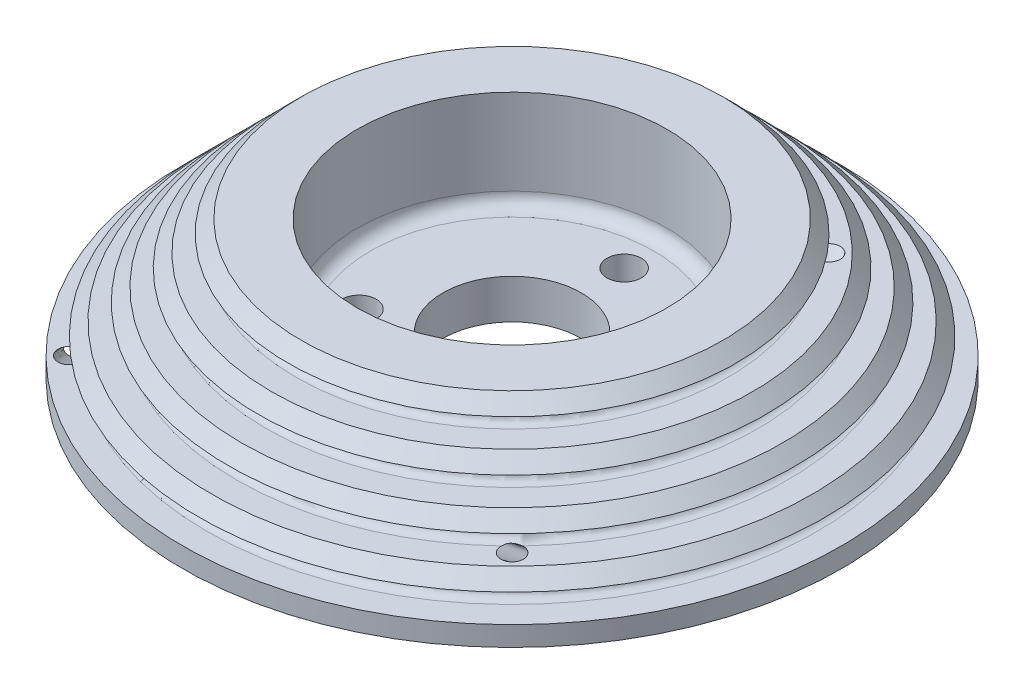
SolidWorks part; units mm, degrees
ref_plane "Front Plane" through (0, 0, 0) normal (0, 0, 1) x (1, 0, 0)
ref_plane "Top Plane" through (0, 0, 0) normal (0, 1, 0) x (1, 0, 0)
ref_plane "Right Plane" through (0, 0, 0) normal (1, 0, 0) x (0, 0, -1)
sketch "Sketch1" plane through (0, 0, 0) normal (0, 0, 1) x (1, 0, 0)
  line L0 (0, 0) -> (0, 21)
  line L1 (0, 21) -> (-32, 21)
  line L2 (-32, 21) -> (-50, 3)
  line L3 (-50, 3) -> (-50, 0)
  line L4 (-50, 0) -> (0, 0)
  dimension "D1" = 50
  dimension "D2" = 21
  dimension "D3" = 45
  dimension "D4" = 3
revolve "Revolve1" add sketch "Sketch1" angle 360 about L0
sketch "Sketch2" plane through (0, 0, 0) normal (0, 0, 1) x (1, 0, 0)
  line L0 (0, 0) -> (0, 23.1188)
  line L1 (-32, 21) -> (-50, 3) construction
  line L2 (-36.5, 19) -> (-31.5, 19)
  line L3 (-36.5, 19) -> (-36.5, 16.5)
  line L4 (-36.5, 16.5) -> (-31.5, 16.5)
  line L5 (-31.5, 19) -> (-31.5, 16.5)
  line L6 (-50, 5.5) -> (-45, 5.5)
  line L7 (-50, 5.5) -> (-50, 3)
  line L8 (-50, 3) -> (-45, 3)
  line L9 (-45, 5.5) -> (-45, 3)
  line L10 (-32, 21) -> (-50, 3)
  line L12 (32, 21) -> (-32, 21) construction
  line L13 (50, 3) -> (-50, 3) construction
  line L15 (-41, 14.5) -> (-36, 14.5)
  line L16 (-41, 14.5) -> (-41, 12)
  line L17 (-41, 12) -> (-36, 12)
  line L18 (-36, 14.5) -> (-36, 12)
  line L19 (-45.5, 10) -> (-40.5, 10)
  line L20 (-45.5, 10) -> (-45.5, 7.5)
  line L21 (-45.5, 7.5) -> (-40.5, 7.5)
  line L22 (-40.5, 10) -> (-40.5, 7.5)
  point P19 (-38.5, 14.5)
  point P26 (-43, 10)
  point P27 (-47.5, 5.5)
  point P28 (-34, 19)
  dimension "D1" = 2.5
  dimension "D2" = 2.5
  dimension "D3" = 5
  dimension "D4" = 5
  dimension "D5" = 5
  dimension "D6" = 2
  dimension "D7" = 2.5
  dimension "D8" = 2
  dimension "D9" = 5
  dimension "D10" = 2.5
  dimension "D11" = 2
revolve "Cut-Revolve1" cut sketch "Sketch2" angle 360 about L0 region at (-46.9444, 4.1111, 0) region at (-42.4444, 8.6111, 0) region at (-37.9444, 13.1111, 0) region at (-33.4444, 17.6111, 0)
fillet "Fillet1" radius 1.25 8 edges at (0, 3, -45) (0, 5.5, -45) (0, 7.5, -40.5) (0, 10, -40.5) (0, 12, -36) (0, 14.5, -36) (0, 16.5, -31.5) (0, 19, -31.5)
sketch "Sketch3" plane through (0, 21, 0) normal (0, 1, 0) x (1, 0, 0)
  line L0 (0, 0) -> (44.738, 0) construction
  line L1 (0, 0) -> (32.1015, 32.1015)
  line L2 (0, 0) -> (32.1015, -32.1015)
  dimension "D1" = 45
ref_plane "top inner hole" through (0, 0, 0) normal (0.7071, 0, 0.7071) x (0.7071, 0, -0.7071)
ref_plane "bottom outer hole" through (0, 0, 0) normal (-0.7071, 0, 0.7071) x (0.7071, 0, 0.7071)
sketch "Sketch4" plane through (0, 0, 0) normal (0.7071, 0, 0.7071) x (0.7071, 0, -0.7071)
  line L0 (34, 16.5) -> (31.0906, 0)
  line L1 (36.5, 16.5) -> (-36.5, 16.5) construction
  line L2 (-50, 0) -> (50, 0) construction
  line L3 (34, 16.5) -> (33.8108, 15.4272)
  line L4 (34, 16.5) -> (34.2703, 18.0328)
  dimension "D1" = 2.5
  dimension "D2" = 80
sketch "Sketch5" plane through (0, 0, 0) normal (-0.7071, 0, 0.7071) x (0.7071, 0, 0.7071)
  line L0 (43, 7.5) -> (40.2702, 0)
  line L1 (45.5, 7.5) -> (-45.5, 7.5) construction
  line L2 (-50, 0) -> (50, 0) construction
  line L3 (43, 7.5) -> (41.2173, 2.6022)
  line L4 (43, 7.5) -> (43.3748, 8.5297)
  dimension "D1" = 2.5
  dimension "D2" = 70
sketch "Sketch6" plane through (0, 0, 0) normal (-0.7071, 0, 0.7071) x (0.7071, 0, 0.7071)
  line L0 (-38.5, 12) -> (-34.1324, 0)
  line L1 (41, 12) -> (-41, 12) construction
  line L2 (-50, 0) -> (50, 0) construction
  line L3 (-38.5, 12) -> (-37.0691, 8.0687)
  line L4 (-38.5, 12) -> (-38.9783, 13.3142)
  dimension "D1" = 70
  dimension "D2" = 2.5
sketch "Sketch7" plane through (0, 0, 0) normal (0.7071, 0, 0.7071) x (0.7071, 0, -0.7071)
  line L0 (-47.5008, 3) -> (-46.4089, 0)
  line L1 (50, 3) -> (-50, 3) construction
  line L2 (-50, 0) -> (50, 0) construction
  line L3 (-47.5008, 3) -> (-45.6338, -2.1294)
  line L4 (-47.5008, 3) -> (-47.9973, 4.3643)
  dimension "D1" = 2.4992
  dimension "D2" = 70
sketch "Sketch8" plane through (0, 16.5, 0) normal (0, 1, 0) x (1, 0, 0)
  circle A0 centre (24.0416, 24.0416) radius 1.7
  dimension "D1" = 3.4
sketch "Sketch9" plane through (0, 7.5, 0) normal (0, 1, 0) x (1, 0, 0)
  circle A0 centre (30.4056, -30.4056) radius 1.7
  dimension "D1" = 3.4
sketch "Sketch10" plane through (0, 3, 0) normal (0, 1, 0) x (1, 0, 0)
  circle A0 centre (-33.5881, -33.5881) radius 1.7
  dimension "D1" = 3.4
sketch "Sketch11" plane through (0, 12, 0) normal (0, 1, 0) x (1, 0, 0)
  circle A0 centre (-27.2236, 27.2236) radius 1.7
  point P3 (0, 0)
  dimension "D1" = 3.4
sketch "Sketch13" plane through (0, 21, 0) normal (0, 1, 0) x (1, 0, 0)
  circle A0 centre (0, 0) radius 23.5
  dimension "D1" = 47
extrude "Cut-Extrude2" cut sketch "Sketch13" against normal blind 15
sketch "Sketch14" plane through (0, 6, 0) normal (0, 1, 0) x (1, 0, 0)
  line L0 (0, 0) -> (0, 23.5) construction
  line L1 (0, 0) -> (20.3516, -11.75) construction
  line L2 (0, 0) -> (-20.3516, -11.75) construction
  circle A0 centre (0, 17) radius 2.6
  circle A1 centre (0, 0) radius 23.5 construction
  circle A2 centre (14.7224, -8.5) radius 2.6
  circle A3 centre (-14.7224, -8.5) radius 2.6
  circle A4 centre (0, 0) radius 10.5
  circle A5 centre (0, 0) radius 19.6
  point P6 (0, 19.6)
  point P16 (0, 0)
  dimension "D1" = 5.2
  dimension "D3" = 21
  dimension "D4" = 17
  dimension "D5" = 19.6
  dimension "D2" = 3
extrude "Cut-Extrude3" cut sketch "Sketch14" against normal through all contours A0 | A3 | A4 | A2 region at (0, 6, -17) region at (-14.7224, 6, 8.5) region at (14.7224, 6, 8.5) region at (0, 6, 0)
fillet "Fillet2" radius 2 1 edges at (0, 6, 23.5)
sketch "Sketch12" plane through (0, 21, 0) normal (0, 1, 0) x (1, 0, 0)
  line L0 (0, 0) -> (0, 13.8549) construction
  line L1 (6.188, 5.3047) -> (9.2093, 7.049)
  line L2 (-1.5, 8.0113) -> (1.5, 8.0113)
  line L3 (-1.5, 8.0113) -> (-1.5, 11.5)
  line L4 (-1.5, 11.5) -> (1.5, 11.5)
  line L5 (1.5, 8.0113) -> (1.5, 11.5)
  line L6 (6.188, 5.3047) -> (7.688, 2.7066)
  line L7 (7.688, 2.7066) -> (10.7093, 4.451)
  line L8 (9.2093, 7.049) -> (10.7093, 4.451)
  line L9 (0, 0) -> (11.9987, 6.9274) construction
  line L10 (7.688, -2.7066) -> (10.7093, -4.451)
  line L11 (7.688, -2.7066) -> (6.188, -5.3047)
  line L12 (6.188, -5.3047) -> (9.2093, -7.049)
  line L13 (10.7093, -4.451) -> (9.2093, -7.049)
  line L14 (0, 0) -> (11.9987, -6.9274) construction
  line L15 (1.5, -8.0113) -> (1.5, -11.5)
  line L16 (1.5, -8.0113) -> (-1.5, -8.0113)
  line L17 (-1.5, -8.0113) -> (-1.5, -11.5)
  line L18 (1.5, -11.5) -> (-1.5, -11.5)
  line L19 (0, 0) -> (0, -13.8549) construction
  line L20 (-6.188, -5.3047) -> (-9.2093, -7.049)
  line L21 (-6.188, -5.3047) -> (-7.688, -2.7066)
  line L22 (-7.688, -2.7066) -> (-10.7093, -4.451)
  line L23 (-9.2093, -7.049) -> (-10.7093, -4.451)
  line L24 (0, 0) -> (-11.9987, -6.9274) construction
  line L25 (-7.688, 2.7066) -> (-10.7093, 4.451)
  line L26 (-7.688, 2.7066) -> (-6.188, 5.3047)
  line L27 (-6.188, 5.3047) -> (-9.2093, 7.049)
  line L28 (-10.7093, 4.451) -> (-9.2093, 7.049)
  line L29 (0, 0) -> (-11.9987, 6.9274) construction
  circle A0 centre (0, 0) radius 10
  point P8 (0, 11.5)
  point P10 (0, 10)
  point P38 (0, 0)
  dimension "D1" = 20
  dimension "D2" = 1.5
  dimension "D3" = 3
  dimension "D4" = 6
ref_plane "Plane1" through (21.3215, -5.3168, -21.3215) normal (-0.6964, 0.1736, 0.6964) x (-0.1228, -0.9848, 0.1228)
sketch "Sketch15" plane through (21.3215, -5.3168, -21.3215) normal (-0.6964, 0.1736, 0.6964) x (-0.1228, -0.9848, 0.1228)
  line L0 (-22.1534, 0) -> (-22.1534, 63.1431) construction
  line L1 (-22.1534, 0) -> (-23.7098, 0) construction
  line L2 (-22.1534, 0) -> (-21.064, 0) construction
  line L3 (-22.1534, 0) -> (26.0239, 83.4456)
  line L4 (-22.1534, 0) -> (-23.3366, -2.0495)
  dimension "D1" = 30
sweep "Cut-Sweep6" cut profiles "Sketch8" path "Sketch15"
ref_plane "Plane2" through (-21.3119, -10.9699, -21.3119) normal (-0.6645, -0.342, -0.6645) x (0.2418, -0.9397, 0.2418)
sketch "Sketch16" plane through (-21.3119, -10.9699, -21.3119) normal (-0.6645, -0.342, -0.6645) x (0.2418, -0.9397, 0.2418)
  line L0 (-24.4441, 0) -> (-24.4441, 66.9619) construction
  line L1 (-24.4441, 0) -> (29.4265, 93.3065)
  line L2 (-24.4441, 0) -> (-25.2774, -1.4434)
  dimension "D1" = 30
sweep "Cut-Sweep7" cut profiles "Sketch11" path "Sketch16"
ref_plane "Plane3" through (-28.9773, -14.9155, 28.9773) normal (-0.6645, -0.342, 0.6645) x (0.2418, -0.9397, -0.2418)
sketch "Sketch17" plane through (-28.9773, -14.9155, 28.9773) normal (-0.6645, -0.342, 0.6645) x (0.2418, -0.9397, -0.2418)
  line L0 (-19.0653, 0) -> (-19.0653, -51.3848) construction
  line L1 (-19.0653, 0) -> (30.6503, -86.1099)
  line L2 (-19.0653, 0) -> (-20.205, 1.974)
  dimension "D1" = 30
sweep "Cut-Sweep8" cut profiles "Sketch10" path "Sketch17"
ref_plane "Plane4" through (25.1444, -12.9426, 25.1444) normal (-0.6645, 0.342, -0.6645) x (-0.2418, -0.9397, -0.2418)
sketch "Sketch18" plane through (25.1444, -12.9426, 25.1444) normal (-0.6645, 0.342, -0.6645) x (-0.2418, -0.9397, -0.2418)
  line L0 (-21.7546, 0) -> (-21.7546, -55.4046) construction
  line L1 (-21.7546, 0) -> (32.4079, -93.8122)
  line L2 (-21.7546, 0) -> (-22.5368, 1.3549)
  dimension "D1" = 30
sweep "Cut-Sweep9" cut profiles "Sketch9" path "Sketch18"
